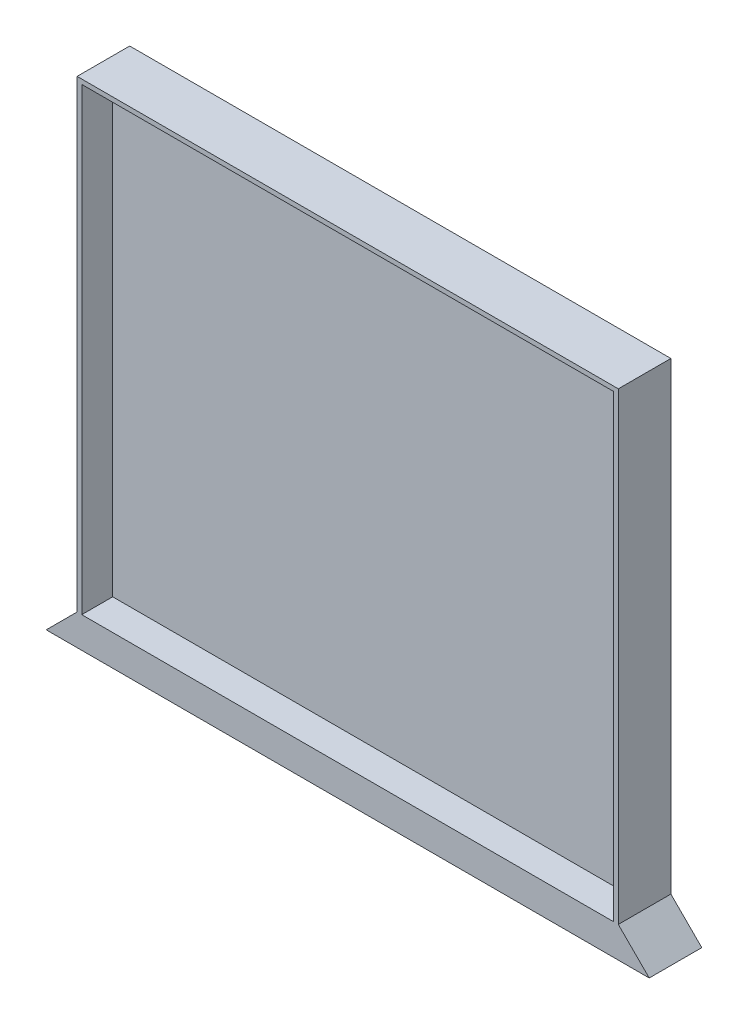
SolidWorks part; units mm, degrees
material "玻璃"
ref_plane "前视基准面" through (0, 0, 0) normal (0, 0, 1) x (1, 0, 0)
ref_plane "上视基准面" through (0, 0, 0) normal (0, 1, 0) x (1, 0, 0)
ref_plane "右视基准面" through (0, 0, 0) normal (1, 0, 0) x (0, 0, -1)
sketch "草图1" plane through (0, 0, 0) normal (0, 0, 1) x (1, 0, 0)
  line L1 (-175, 160) -> (175, 160)
  line L2 (-175, 160) -> (-175, -160)
  line L3 (-175, -160) -> (175, -160)
  line L4 (175, 160) -> (175, -160)
  line L5 (-175, 160) -> (175, -160) construction
  line L6 (-175, -160) -> (175, 160) construction
  point P0 (0, 0)
  dimension "D1" = 350
  dimension "D2" = 320
extrude "凸台-拉伸1" add sketch "草图1" along normal blind 34
sketch "草图2" plane through (0, 0, 34) normal (0, 0, 1) x (1, 0, 0)
  line L0 (175, 160) -> (-175, 160) construction
  line L1 (-172, 157) -> (172, 157)
  line L2 (-172, 157) -> (-172, -157)
  line L3 (-172, -157) -> (172, -157)
  line L4 (172, 157) -> (172, -157)
  line L5 (-172, 157) -> (172, -157) construction
  line L6 (-172, -157) -> (172, 157) construction
  line L7 (-175, 160) -> (-175, -160) construction
  point P0 (0, 0)
  dimension "D1" = 3
  dimension "D2" = 3
extrude "切除-拉伸1" cut sketch "草图2" against normal blind 20
sketch "草图3" plane through (0, -160, 0) normal (0, -1, 0) x (1, 0, 0)
  line L1 (-195, 34) -> (195, 34)
  line L2 (-195, 34) -> (-195, 0)
  line L3 (-195, 0) -> (195, 0)
  line L4 (195, 34) -> (195, 0)
  line L5 (-195, 34) -> (195, 0) construction
  line L6 (-195, 0) -> (195, 34) construction
  point P0 (0, 17)
  dimension "D1" = 34
  dimension "D2" = 17
  dimension "D3" = 390
extrude "凸台-拉伸2" add sketch "草图3" against normal blind 20
chamfer "倒角1" distance 20 angle 45 2 edges at (195, -140, 17) (-195, -140, 17)
